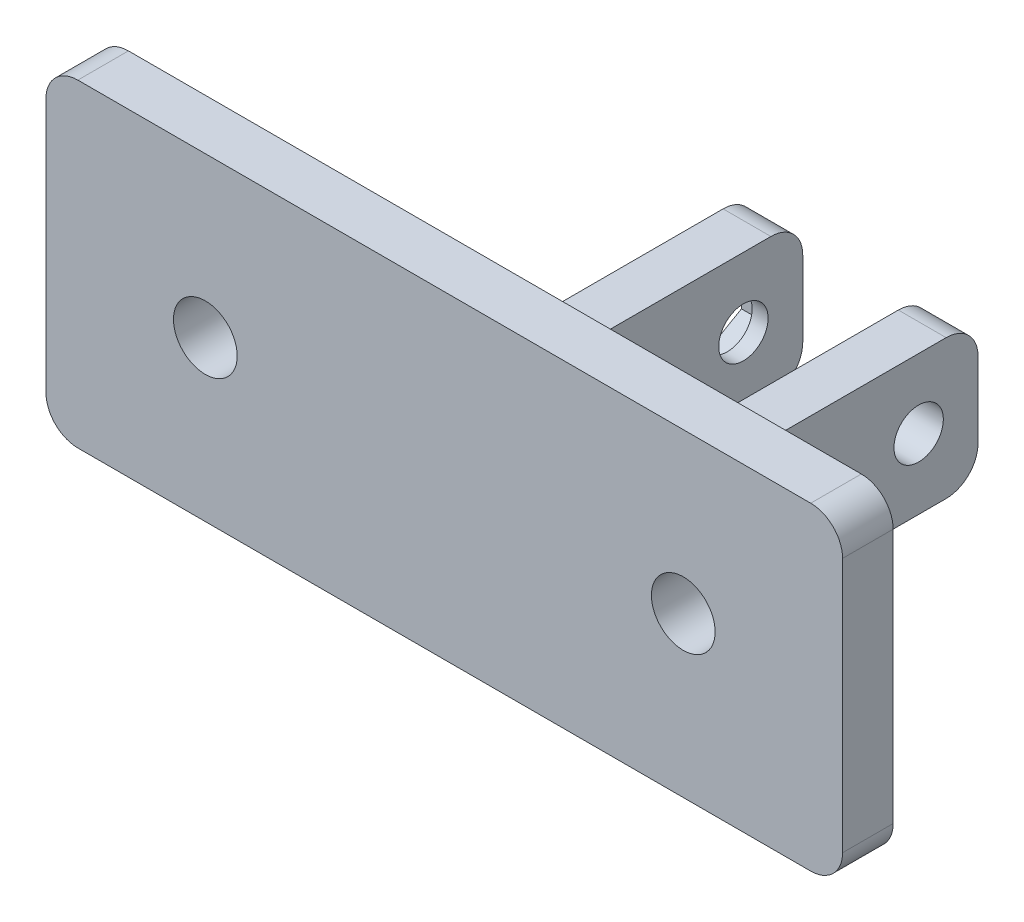
SolidWorks part; units mm, degrees
ref_plane "Front Plane" through (0, 0, 0) normal (0, 0, 1) x (1, 0, 0)
ref_plane "Top Plane" through (0, 0, 0) normal (0, 1, 0) x (1, 0, 0)
ref_plane "Right Plane" through (0, 0, 0) normal (1, 0, 0) x (0, 0, -1)
sketch "Sketch1" plane through (0, 0, 0) normal (0, 0, 1) x (1, 0, 0)
  line L0 (-15, 0) -> (15, 0) construction
  line L1 (-25, -10) -> (25, -10)
  line L2 (-25, -10) -> (-25, 10)
  line L3 (-25, 10) -> (25, 10)
  line L4 (25, -10) -> (25, 10)
  line L5 (-25, -10) -> (25, 10) construction
  line L6 (-25, 10) -> (25, -10) construction
  circle A0 centre (-15, 0) radius 2
  circle A1 centre (15, 0) radius 2
  point P0 (0, 0)
  point P9 (0, 0)
  dimension "D3" = 4
  dimension "D1" = 50
  dimension "D2" = 20
  dimension "D4" = 30
extrude "Boss-Extrude1" add sketch "Sketch1" along normal blind 3.175
sketch "Sketch3" plane through (0, 0, 0) normal (1, 0, 0) x (0, 0, -1)
  line L1 (-3.175, -10) -> (23.325, -10)
  line L2 (-3.175, -10) -> (-3.175, -1.25)
  line L3 (-3.175, -1.25) -> (23.325, -1.25)
  line L4 (23.325, -10) -> (23.325, -1.25)
  line L6 (-3.175, -10) -> (-3.175, 10) construction
  line L7 (3.6, -5.6) -> (19.6, -5.6) construction
  line L8 (6.475, -3.9401) -> (3.6, -2.2802)
  line L9 (3.6, -2.2802) -> (0.725, -3.9401)
  line L10 (0.725, -3.9401) -> (0.725, -7.2599)
  line L11 (0.725, -7.2599) -> (3.6, -8.9198)
  line L12 (3.6, -8.9198) -> (6.475, -7.2599)
  line L13 (6.475, -7.2599) -> (6.475, -3.9401)
  line L14 (-3.175, -10) -> (0, -10) construction
  line L15 (22.475, -3.9401) -> (19.6, -2.2802)
  line L16 (19.6, -2.2802) -> (16.725, -3.9401)
  line L17 (16.725, -3.9401) -> (16.725, -7.2599)
  line L18 (16.725, -7.2599) -> (19.6, -8.9198)
  line L19 (19.6, -8.9198) -> (22.475, -7.2599)
  line L20 (22.475, -7.2599) -> (22.475, -3.9401)
  circle A0 centre (3.6, -5.6) radius 1.55
  circle A1 centre (19.6, -5.6) radius 1.55
  circle A2 centre (3.6, -5.6) radius 2.875 construction
  circle A3 centre (19.6, -5.6) radius 2.875 construction
  point P26 (23.8634, -1.9464)
  point P27 (24.7844, -10.5731)
  point P28 (23.2187, -1.1789)
  dimension "D2" = 3.1
  dimension "D4" = 5.75
  dimension "D1" = 6.775
  dimension "D3" = 16
  dimension "D5" = 4.4
  dimension "D6" = 8.75
  dimension "D7" = 26.5
extrude "Boss-Extrude2" add sketch "Sketch3" along normal blind 3 from offset 4 contours L1 L4 L3 L2 L20 L19 L18 L17 L16 L15 L13 L12 L11 L10 L9 L8 | L12 L13 L8 L9 L10 L11 A0 | L19 L20 L15 L16 L17 L18 A1 region at (0, -5.6332, -9.5749) region at (0, -5.6, -6.3872) region at (0, -5.6, -22.3872)
mirror "Mirror1" about plane through (0, 0, 0) normal (1, 0, 0) of "Boss-Extrude2"
extrude "Cut-Extrude1" cut sketch "Sketch3<3>" along normal blind 2 from surface contours L12 L13 L8 L9 L10 L11 A0 | L19 L20 L15 L16 L17 L18 A1 region at (0, -5.6, -6.3872) region at (0, -5.6, -22.3872) starting at face at (-7, -5.625, -11.6625)
sketch "Sketch3<3>" plane through (0, 0, 0) normal (1, 0, 0) x (0, 0, -1) same geometry as "Sketch3"
fillet "Fillet1" radius 2 2 edges at (-5.5, -1.25, 0) (5.5, -1.25, 0)
fillet "Fillet2" radius 2 8 edges at (-25, 10, 1.5875) (25, 10, 1.5875) (25, -10, 1.5875) (-25, -10, 1.5875) (-5.5, -10, -23.325) (-5.5, -1.25, -23.325) (5.5, -1.25, -23.325) (5.5, -10, -23.325)
sketch "Sketch4" plane through (0, 0, 0) normal (0, 0, -1) x (-1, 0, 0)
  line L0 (23, -8) -> (23, 8)
  line L1 (23, 8) -> (-23, 8)
  line L2 (-23, 8) -> (-23, -8)
  line L3 (-23, -8) -> (-9, -8)
  line L4 (-9, -8) -> (-9, 2.75)
  line L5 (-9, 2.75) -> (-2, 2.75)
  line L6 (-2, 2.75) -> (-2, -8)
  line L7 (-2, -8) -> (2, -8)
  line L8 (2, -8) -> (2, 2.75)
  line L9 (2, 2.75) -> (9, 2.75)
  line L10 (9, 2.75) -> (9, -8)
  line L11 (9, -8) -> (23, -8)
  line L12 (25, -8) -> (25, 8)
  line L13 (23, 10) -> (-23, 10)
  line L14 (-25, 8) -> (-25, -8)
  line L15 (-23, -10) -> (-7, -10)
  line L16 (-7, -10) -> (-7, 0.75)
  line L17 (-7, 0.75) -> (-4, 0.75)
  line L18 (-4, 0.75) -> (-4, -10)
  line L19 (-4, -10) -> (4, -10)
  line L20 (4, -10) -> (4, 0.75)
  line L21 (4, 0.75) -> (7, 0.75)
  line L22 (7, 0.75) -> (7, -10)
  line L23 (7, -10) -> (23, -10)
  line L24 (25, -8) -> (25, 8)
  line L25 (23, 10) -> (-23, 10)
  line L26 (-25, 8) -> (-25, -8)
  line L27 (-23, -10) -> (-7, -10)
  line L28 (-7, -10) -> (-7, 0.75)
  line L29 (-7, 0.75) -> (-4, 0.75)
  line L30 (-4, 0.75) -> (-4, -10)
  line L31 (-4, -10) -> (4, -10)
  line L32 (4, -10) -> (4, 0.75)
  line L33 (4, 0.75) -> (7, 0.75)
  line L34 (7, 0.75) -> (7, -10)
  line L35 (7, -10) -> (23, -10)
  arc A0 (23, 8) -> (23, 8) centre (23, 8) ccw
  arc A1 (-23, 8) -> (-23, 8) centre (-23, 8) ccw
  arc A2 (-23, -8) -> (-23, -8) centre (-23, -8) ccw
  arc A3 (23, -8) -> (23, -8) centre (23, -8) ccw
  arc A4 (25, 8) -> (23, 10) centre (23, 8) ccw
  arc A5 (-23, 10) -> (-25, 8) centre (-23, 8) ccw
  arc A6 (-25, -8) -> (-23, -10) centre (-23, -8) ccw
  arc A7 (23, -10) -> (25, -8) centre (23, -8) ccw
  arc A8 (25, 8) -> (23, 10) centre (23, 8) ccw
  arc A9 (-23, 10) -> (-25, 8) centre (-23, 8) ccw
  arc A10 (-25, -8) -> (-23, -10) centre (-23, -8) ccw
  arc A11 (23, -10) -> (25, -8) centre (23, -8) ccw
  circle A17 centre (-15, 0) radius 4
  circle A18 centre (-15, 0) radius 4
  circle A20 centre (15, 0) radius 4
  circle A21 centre (15, 0) radius 4
  dimension "D1" = 0
  dimension "D2" = 2
  dimension "D3" = 2
  dimension "D4" = 2
extrude "Cut-Extrude2" cut sketch "Sketch4" against normal blind 1.5 contours L10 L11 L0 L1 L2 L3 L4 L5 L6 L7 L8 L9 A21 A18 region at (0, 0.8146, 0)
fillet "Fillet3" radius 1.5 12 edges at (-9, 2.75, 0.75) (-2, 2.75, 0.75) (-2, -8, 0.75) (2, -8, 0.75) (2, 2.75, 0.75) (9, 2.75, 0.75) (9, -8, 0.75) (23, -8, 0.75) (-23, 8, 0.75) (-23, -8, 0.75) (-9, -8, 0.75) (23, 8, 0.75)
fillet "Fillet4" radius 1 26 edges at (1.5607, -7.5607, 1.5) (2, -2.625, 1.5) (2.4393, 2.3107, 1.5) (5.5, 2.75, 1.5) (8.5607, 2.3107, 1.5) (9, -2.625, 1.5) (9.4393, -7.5607, 1.5) (16, -8, 1.5) (22.5607, -7.5607, 1.5) (23, 0, 1.5) (22.5607, 7.5607, 1.5) (0, 8, 1.5) (-22.5607, 7.5607, 1.5) (-23, 0, 1.5) (-22.5607, -7.5607, 1.5) (-16, -8, 1.5) (-9.4393, -7.5607, 1.5) (-9, -2.625, 1.5) (-8.5607, 2.3107, 1.5) (-5.5, 2.75, 1.5) (-2.4393, 2.3107, 1.5) (-2, -2.625, 1.5) (-1.5607, -7.5607, 1.5) (0, -8, 1.5) (11, 0, 1.5) (-19, 0, 1.5)
